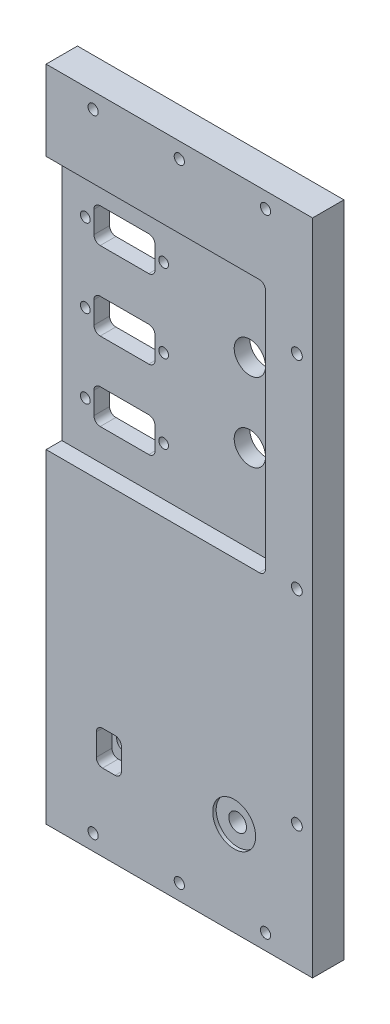
SolidWorks part; units mm, degrees
ref_plane "Front Plane" through (0, 0, 0) normal (0, 0, 1) x (1, 0, 0)
ref_plane "Top Plane" through (0, 0, 0) normal (0, 1, 0) x (1, 0, 0)
ref_plane "Right Plane" through (0, 0, 0) normal (1, 0, 0) x (0, 0, -1)
sketch "Sketch1" plane through (0, 0, 0) normal (0, 0, 1) x (1, 0, 0)
  line L1 (-158.3632, 91.8414) -> (-73.3632, 91.8414)
  line L2 (-158.3632, 91.8414) -> (-158.3632, -118.1586)
  line L3 (-158.3632, -118.1586) -> (-73.3632, -118.1586)
  line L4 (-73.3632, 91.8414) -> (-73.3632, -118.1586)
  dimension "D1" = 210
  dimension "D2" = 85
extrude "Boss-Extrude1" add sketch "Sketch1" along normal blind 10
sketch "Sketch2" plane through (0, 0, 10) normal (0, 0, 1) x (1, 0, 0)
  line L0 (-138.3632, 31.3414) -> (-138.3632, 20.3414)
  line L9 (-138.3632, 56.3414) -> (-138.3632, 45.3414)
  line L14 (-148.1132, 56.3414) -> (-128.6132, 56.3414)
  line L24 (-158.3632, 91.8414) -> (-158.3632, -118.1586) construction
  line L25 (-142.3632, -93.6586) -> (-134.3632, -93.6586)
  line L26 (-142.3632, -93.6586) -> (-142.3632, -82.6586)
  line L27 (-142.3632, -82.6586) -> (-134.3632, -82.6586)
  line L28 (-134.3632, -93.6586) -> (-134.3632, -82.6586)
  line L29 (-142.3632, -93.6586) -> (-134.3632, -82.6586) construction
  line L30 (-142.3632, -82.6586) -> (-134.3632, -93.6586) construction
  line L31 (-148.1132, 56.3414) -> (-148.1132, 45.3414)
  line L32 (-148.1132, 45.3414) -> (-128.6132, 45.3414)
  line L33 (-128.6132, 56.3414) -> (-128.6132, 45.3414)
  line L34 (-148.1132, 31.3414) -> (-128.6132, 31.3414)
  line L35 (-148.1132, 31.3414) -> (-148.1132, 20.3414)
  line L36 (-148.1132, 20.3414) -> (-128.6132, 20.3414)
  line L37 (-128.6132, 31.3414) -> (-128.6132, 20.3414)
  line L38 (-138.3632, 6.3414) -> (-138.3632, -4.6586)
  line L39 (-148.1132, 6.3414) -> (-128.6132, 6.3414)
  line L40 (-148.1132, 6.3414) -> (-148.1132, -4.6586)
  line L41 (-148.1132, -4.6586) -> (-128.6132, -4.6586)
  line L42 (-128.6132, 6.3414) -> (-128.6132, -4.6586)
  line L43 (-128.6132, 45.3414) -> (-128.6132, 31.3414)
  line L44 (-128.6132, 20.3414) -> (-128.6132, 6.3414)
  line L45 (-73.3632, -118.1586) -> (-73.3632, 91.8414) construction
  line L46 (-158.3632, -118.1586) -> (-73.3632, -118.1586) construction
  line L47 (-158.3632, 66.3414) -> (-88.3632, 66.3414)
  line L48 (-158.3632, 66.3414) -> (-158.3632, -14.6586)
  line L49 (-158.3632, -14.6586) -> (-88.3632, -14.6586)
  line L50 (-88.3632, 66.3414) -> (-88.3632, -14.6586)
  circle A6 centre (-98.3632, 38.3414) radius 5
  circle A7 centre (-98.3632, 13.3414) radius 5
  circle A8 centre (-138.3632, -88.1586) radius 2.5
  circle A9 centre (-125.8632, 50.8414) radius 1.55
  circle A10 centre (-150.8632, 50.8414) radius 1.55
  circle A11 centre (-125.8632, 25.8414) radius 1.55
  circle A12 centre (-150.8632, 25.8414) radius 1.55
  circle A13 centre (-125.8632, 0.8414) radius 1.55
  circle A14 centre (-150.8632, 0.8414) radius 1.55
  point P25 (-138.3632, 50.8414)
  point P37 (-128.6132, 38.3414)
  point P44 (-128.6132, 13.3414)
  point P47 (-138.3632, -88.1586)
  dimension "D5" = 3.1
  dimension "D10" = 10
  dimension "D11" = 10
  dimension "D13" = 19.5
  dimension "D17" = 0
  dimension "D20" = 5
  dimension "D8" = 0
  dimension "D3" = 0
  dimension "D6" = 3
  dimension "D7" = 0
  dimension "D9" = 25
  dimension "D12" = 11
  dimension "D14" = 25
  dimension "D15" = 0
  dimension "D16" = 25
  dimension "D18" = 10
  dimension "D19" = 10
  dimension "D21" = 30
  dimension "D22" = 11
  dimension "D23" = 8
  dimension "D24" = 20
  dimension "D25" = 10
extrude "RS232 & BNC feedthroughs" cut sketch "Sketch2" against normal up to next contours A7 | A6 region at (-98.3632, 13.3414, 10)
extrude "LED thru hole" cut sketch "Sketch2<3>" against normal up to next contours A8
sketch "Sketch2<3>" plane through (0, 0, 10) normal (0, 0, 1) x (1, 0, 0) same geometry as "Sketch2"
sketch "Sketch3" plane through (0, 0, 10) normal (0, 0, 1) x (1, 0, 0)
  line L1 (-73.3632, -118.1586) -> (-73.3632, 91.8414) construction
  circle A0 centre (-98.3632, -88.1586) radius 2.8296
  circle A1 centre (-98.3632, -88.1586) radius 6.85
  dimension "D1" = 5.6591
  dimension "D2" = 13.7
  dimension "D3" = 0
  dimension "D4" = 25
extrude "1/4-40 threaded through hole" cut sketch "Sketch3" against normal up to next contours A0
extrude "switch recess" cut sketch "Sketch3<3>" against normal offset from surface (1.1 mm away) 8.9 up to face at (-95.5336, -88.1586, 0)
sketch "Sketch3<3>" plane through (0, 0, 10) normal (0, 0, 1) x (1, 0, 0) same geometry as "Sketch3"
sketch "Sketch4" plane through (0, 0, 0) normal (0, 0, -1) x (-1, 0, 0)
  line L0 (73.3632, -13.1586) -> (158.3632, -13.1586)
  line L1 (73.3632, -118.1586) -> (73.3632, 91.8414) construction
  line L2 (158.3632, 91.8414) -> (158.3632, -118.1586) construction
  line L3 (78.3632, -78.1586) -> (78.3632, 51.8414)
  line L4 (73.3632, -118.1586) -> (73.3632, 91.8414) construction
  point P9 (78.3632, -13.1586)
  dimension "D1" = 130
  dimension "D2" = 5
hole_wizard "CBORE for #4 Binding Head Machine Screw1" positions "Sketch5" profile "Sketch6" counterbore size "#4" standard "ANSI Inch" end condition through all
sketch "Sketch5" plane through (0, 0, 0) normal (0, 0, -1) x (-1, 0, 0)
  line L0 (78.3632, -78.1586) -> (78.3632, 51.8414) construction
  point P0 (78.3632, 51.8414)
  point P3 (78.3632, -13.1586)
  point P7 (78.3632, -78.1586)
sketch "Sketch6" plane through (-78.3632, 51.8414, 0) normal (1, 0, 0) x (0, 1, 0)
  line L0 (0, 0) -> (0, 10)
  line L1 (0, 10) -> (1.7272, 10)
  line L3 (1.7272, 10) -> (1.7272, 1.7272)
  line L4 (1.7272, 1.7272) -> (3.3731, 1.7272)
  line L5 (3.3731, 1.7272) -> (3.3731, 0)
  line L7 (3.3731, 0) -> (0, 0)
  line L11 (0, -6.35) -> (0, 107.95) construction
  dimension "Thru Hole Dia." = 3.4544
  dimension "Thru Hole Depth" = 10
  dimension "C'Bore Dia." = 6.7462
  dimension "C'Bore Depth" = 1.7272
extrude "RS232 feedthrus" cut sketch "Sketch2<7>" against normal up to next contours L31 L32 L9 L14 | L33 L14 L9 L32 | L35 L36 L0 L34 | L37 L34 L0 L36 | L42 L39 L38 L41 | L40 L41 L38 L39 | A9 | A10 | A12 | A11 | A14 | A13 region at (-133.4882, 25.8414, 10) region at (-143.2382, 25.8414, 10) region at (-133.4882, 50.8414, 10) region at (-133.4882, 0.8414, 10) region at (-143.2382, 50.8414, 10) region at (-143.2382, 0.8414, 10)
sketch "Sketch2<7>" plane through (0, 0, 10) normal (0, 0, 1) x (1, 0, 0) same geometry as "Sketch2"
extrude "Cut-Extrude6" cut sketch "Sketch2<8>" against normal blind 5 contours L50 L47 L48 L49 A12 A11 L14 L33 L37 L42 L41 L40 L39 L36 L35 L34 L32 L31 A6 A7 A9 A10 A13 A14 | L25 L28 L27 L26 A8 region at (-142.2272, -88.1586, 10) region at (-122.0355, 25.8414, 10)
sketch "Sketch2<8>" plane through (0, 0, 10) normal (0, 0, 1) x (1, 0, 0) same geometry as "Sketch2"
fillet "Fillet4" radius 2 18 edges at (-88.3632, -14.6586, 7.5) (-88.3632, 66.3414, 7.5) (-128.6132, 31.3414, 2.5) (-148.1132, 31.3414, 2.5) (-148.1132, 20.3414, 2.5) (-128.6132, 20.3414, 2.5) (-128.6132, -4.6586, 2.5) (-128.6132, 6.3414, 2.5) (-148.1132, 6.3414, 2.5) (-148.1132, -4.6586, 2.5) (-128.6132, 45.3414, 2.5) (-148.1132, 45.3414, 2.5) (-128.6132, 56.3414, 2.5) (-148.1132, 56.3414, 2.5) (-134.3632, -93.6586, 7.5) (-142.3632, -93.6586, 7.5) (-142.3632, -82.6586, 7.5) (-134.3632, -82.6586, 7.5)
sketch "Sketch8" plane through (0, 0, 0) normal (0, 0, -1) x (-1, 0, 0)
  line L0 (143.3632, 86.8414) -> (88.3632, 86.8414)
  line L1 (158.3632, 91.8414) -> (158.3632, -118.1586) construction
  line L2 (73.3632, 91.8414) -> (158.3632, 91.8414) construction
  line L3 (158.3632, -13.1586) -> (73.3632, -13.1586)
  line L4 (143.3632, -113.1586) -> (88.3632, -113.1586)
  point P3 (115.8632, 86.8414)
  point P7 (115.8632, 91.8414)
  dimension "D1" = 15
  dimension "D2" = 0
  dimension "D3" = 5
hole_wizard "CBORE for #4 Binding Head Machine Screw2" positions "Sketch9" profile "Sketch10" counterbore size "#4" standard "ANSI Inch" end condition up to next
sketch "Sketch9" plane through (0, 0, 0) normal (0, 0, -1) x (-1, 0, 0)
  line L0 (143.3632, -113.1586) -> (88.3632, -113.1586) construction
  point P0 (143.3632, 86.8414)
  point P3 (115.8632, 86.8414)
  point P6 (88.3632, 86.8414)
  point P9 (88.3632, -113.1586)
  point P12 (115.8632, -113.1586)
  point P16 (143.3632, -113.1586)
sketch "Sketch10" plane through (-143.3632, 86.8414, 0) normal (1, 0, 0) x (0, 1, 0)
  line L0 (0, 0) -> (0, 10)
  line L1 (0, 10) -> (1.6319, 10)
  line L3 (1.6319, 10) -> (1.632, 1.7272)
  line L4 (1.632, 1.7272) -> (3.3731, 1.7272)
  line L5 (3.3731, 1.7272) -> (3.3731, 0)
  line L7 (3.3731, 0) -> (0, 0)
  line L11 (0, -6.35) -> (0, 107.95) construction
  dimension "Thru Hole Dia." = 3.2639
  dimension "Thru Hole Depth" = 10
  dimension "C'Bore Dia." = 6.7462
  dimension "C'Bore Depth" = 1.7272
sketch "Sketch11" plane through (-158.3632, 0, 0) normal (-1, 0, 0) x (0, 0, 1)
  line L0 (5, -118.1586) -> (5, 91.8414)
  line L1 (10, -118.1586) -> (0, -118.1586) construction
  line L2 (10, 91.8414) -> (0, 91.8414) construction
  point P6 (5, -63.1586)
  point P7 (5, -13.1586)
  dimension "D1" = 50
hole_wizard "#4-40 Tapped Hole1" positions "Sketch12" profile "Sketch13" tap size "#4-40" standard "ANSI Inch"
sketch "Sketch12" plane through (-158.3632, 0, 0) normal (-1, 0, 0) x (0, 0, 1)
  point P0 (5, -63.1586)
sketch "Sketch13" plane through (-158.3632, -63.1586, 5) normal (0, 1, 0) x (0, 0, 1)
  line L0 (0, 0) -> (0, 8.2792)
  line L1 (0, 8.2792) -> (1.1303, 7.6)
  line L2 (1.1303, 7.6) -> (1.1303, 0)
  line L5 (1.1303, 0) -> (0, 0)
  line L10 (0, 8.2792) -> (-1.1303, 7.6) construction
  line L11 (0, -6.35) -> (0, 107.95) construction
  dimension "Tap Drill Dia." = 2.2606
  dimension "Tap Drill Depth" = 7.6
  dimension "Drill Angle" = 118
cosmetic thread "Hole Thread1" parameters "D1"=5.69, "D2"=2.8448
